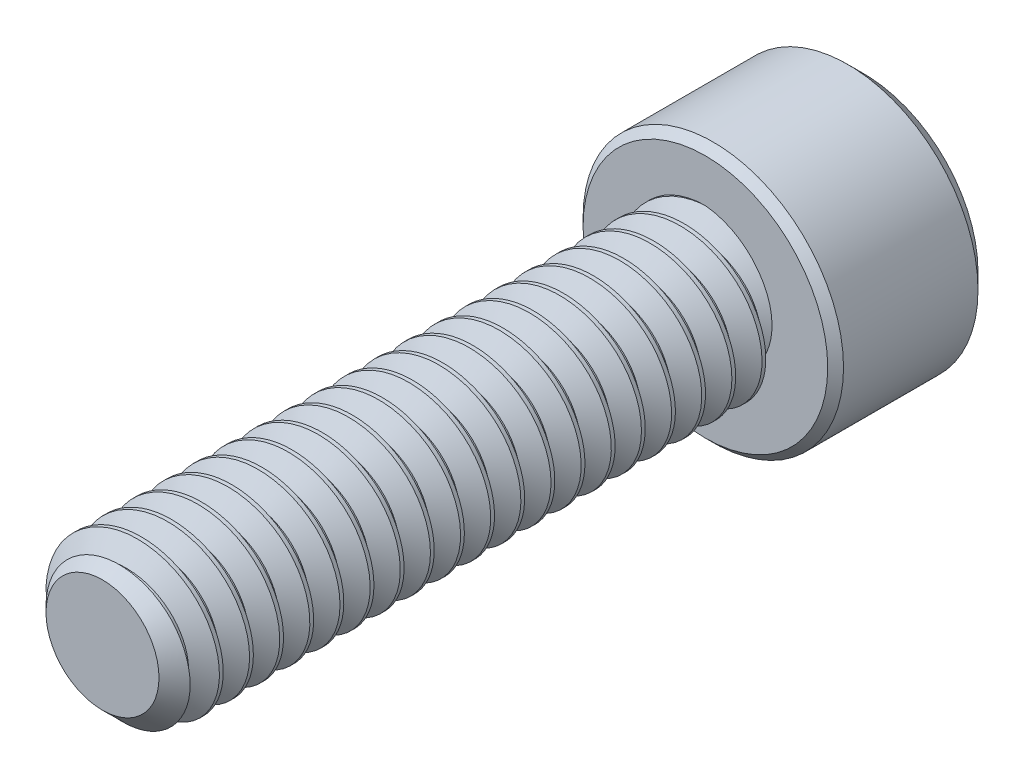
SolidWorks part; units mm, degrees
ref_plane "Front Plane" through (0, 0, 0) normal (0, 0, 1) x (1, 0, 0)
ref_plane "Top Plane" through (0, 0, 0) normal (0, 1, 0) x (1, 0, 0)
ref_plane "Right Plane" through (0, 0, 0) normal (1, 0, 0) x (0, 0, -1)
sketch "Sketch1" plane through (0, 0, 0) normal (0, 0, 1) x (1, 0, 0)
  line L0 (0, 2.0828) -> (0, -2.0828) construction
  circle A0 centre (0, 0) radius 2.0828
  dimension "OD" = 4.1656
extrude "Extrude1" add sketch "Sketch1" against normal blind 15.875
sketch "Sketch2" plane through (0, 0, 0) normal (0, 0, 1) x (1, 0, 0)
  circle A0 centre (0, 0) radius 2.0828 construction
  circle A1 centre (0, 0) radius 2.0828
curve "Helix/Spiral1" pitch 0.7937 height 16.6687 turns 21 parameters "pitch"=0.7937
chamfer "Chamfer3" distance 0.5953 angle 45 1 edges at (2.0828, 0, 0)
sketch "Sketch3" plane through (0, 0, 0) normal (1, 0, 0) x (0, 0, -1)
  line L0 (-0.6945, 2.0828) -> (-0.3969, 1.5672)
  line L1 (-0.3969, 1.5672) -> (-0.2977, 1.5672)
  line L2 (-0.2977, 1.5672) -> (0, 2.0828)
  line L3 (-0.6945, 2.0828) -> (0, 2.0828)
  line L4 (-0.3473, 2.0828) -> (-0.3473, 1.5672) construction
  line L5 (-0.5457, 1.825) -> (-0.1488, 1.825) construction
  line L6 (0, 2.0828) -> (0, -2.0828) construction
  dimension "D1" = 0.0992
  dimension "D2" = 0.3969
  dimension "D3" = 60
sweep "Cut-Sweep1" cut profiles "Sketch3" path "Helix/Spiral1"
sketch "Sketch6" plane through (0, 0, -15.875) normal (0, 0, -1) x (-1, 0, 0)
  circle A0 centre (0, 0) radius 3.429
  dimension "head dia" = 6.858
extrude "Extrude2" add sketch "Sketch6" along normal blind 4.1656
sketch "Sketch7" plane through (0, 0, -20.0406) normal (0, 0, -1) x (-1, 0, 0)
  line L1 (0, 2.0622) -> (-1.7859, 1.0311)
  line L2 (-1.7859, 1.0311) -> (-1.7859, -1.0311)
  line L3 (-1.7859, -1.0311) -> (0, -2.0622)
  line L4 (0, -2.0622) -> (1.7859, -1.0311)
  line L5 (1.7859, -1.0311) -> (1.7859, 1.0311)
  line L6 (1.7859, 1.0311) -> (0, 2.0622)
  circle A0 centre (0, 0) radius 1.7859 construction
  dimension "hex dia" = 3.5719
extrude "Cut-Extrude1" cut sketch "Sketch7" against normal blind 2.6789
sketch "Sketch8" plane through (0, 0, -20.0406) normal (0, 0, -1) x (-1, 0, 0)
  circle A0 centre (0, 0) radius 2.0622
extrude "Cut-Extrude2" cut sketch "Sketch8" against normal blind 0.4166 draft 45
chamfer "Chamfer1" distance 0.4166 angle 45 1 edges at (-3.429, 0, -20.0406)
chamfer "Chamfer2" distance 0.2083 angle 45 1 edges at (-3.429, 0, -15.875)
sketch "Sketch9" plane through (0, 0, 0) normal (1, 0, 0) x (0, 0, -1)
  line L0 (0, 2.0828) -> (0, -2.0828) construction
  line L1 (4.3656, 2.0828) -> (4.3656, -2.0828) construction
  line L2 (15.875, 3.429) -> (15.875, -3.429) construction
  line L3 (20.0406, 3.429) -> (20.0406, -3.429) construction
  line L4 (20.0406, 0) -> (0, 0) construction
  dimension "D1" = 4.3656
  dimension "D2" = 4.1656
  dimension "D3" = 6.858
  dimension "D4" = 15.875
equation "\"D3@Helix/Spiral1\" = \"screw length@Extrude1\"+\"pitch@Helix/Spiral1\""
equation "\"D1@Sketch3\" = \"pitch@Helix/Spiral1\"*.125"
equation "\"D2@Sketch3\" = \"pitch@Helix/Spiral1\"*.5"
equation "\"D1@Cut-Extrude1\" = \"hex dia@Sketch7\"*.75"
equation "\"D1@Chamfer1\" = \"head depth@Extrude2\"/10"
equation "\"D1@Sketch9\" = \"pitch@Helix/Spiral1\"*5.5"
equation "\"D1@Chamfer2\" = \"D1@Chamfer1\"/2"
equation "\"D1@Cut-Extrude2\" = \"D1@Chamfer2\"*2"
equation "\"D1@Chamfer3\" = \"pitch@Helix/Spiral1\"*.750"
equation "\"D2@Sketch9\" = \"head depth@Extrude2\""
equation "\"D3@Sketch9\" = \"head dia@Sketch6\""
equation "\"D4@Sketch9\" = \"screw length@Extrude1\""
